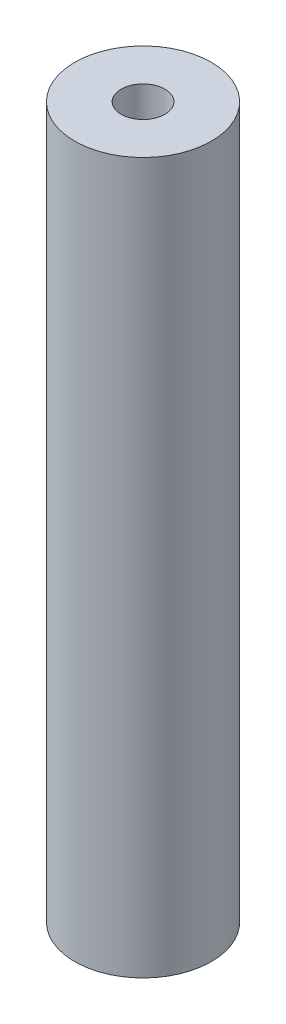
SolidWorks part; units mm, degrees
ref_plane "Front" through (0, 0, 0) normal (0, 0, 1) x (1, 0, 0)
ref_plane "Top" through (0, 0, 0) normal (0, 1, 0) x (1, 0, 0)
ref_plane "Right" through (0, 0, 0) normal (1, 0, 0) x (0, 0, -1)
ref_axis "X" through (-80.9, 0, 0) along (1, 0, 0)
ref_axis "Y" through (0, -50, 0) along (0, 1, 0)
ref_axis "Z" through (0, 0, -80.9) along (0, 0, 1)
sketch "Sketch1" plane through (0, 0, 0) normal (0, 1, 0) x (1, 0, 0)
  circle A0 centre (0, 0) radius 2.5
  dimension "D1" = 5
extrude "Boss-Extrude1" add sketch "Sketch1" along normal mid plane 26
hole_wizard "M2x0.4 Tapped Hole1" positions "3DSketch1" profile "Sketch2" tap size "M2x0.4" standard "ANSI Metric"
sketch3d "3DSketch1"
  line L0 (0, -13, 0) -> (0, 0, 0) construction
  line L1 (0, 0, 0) -> (0, 13, 0) construction
  point P0 (0, 13, 0)
  point P2 (0, -13, 0)
sketch "Sketch2" plane through (0, 13, 0) normal (1, 0, 0) x (0, 0, 1)
  line L0 (0, 0) -> (0, 5.6807)
  line L1 (0, 5.6807) -> (0.8, 5.2)
  line L2 (0.8, 5.2) -> (0.8, 0)
  line L5 (0.8, 0) -> (0, 0)
  line L10 (0, 5.6807) -> (-0.8, 5.2) construction
  line L11 (0, -6.35) -> (0, 107.95) construction
  dimension "Tap Drill Dia." = 1.6
  dimension "Tap Drill Depth" = 5.2
  dimension "Drill Angle" = 118
cosmetic thread "Hole Thread1"
cosmetic thread "Hole Thread2"
